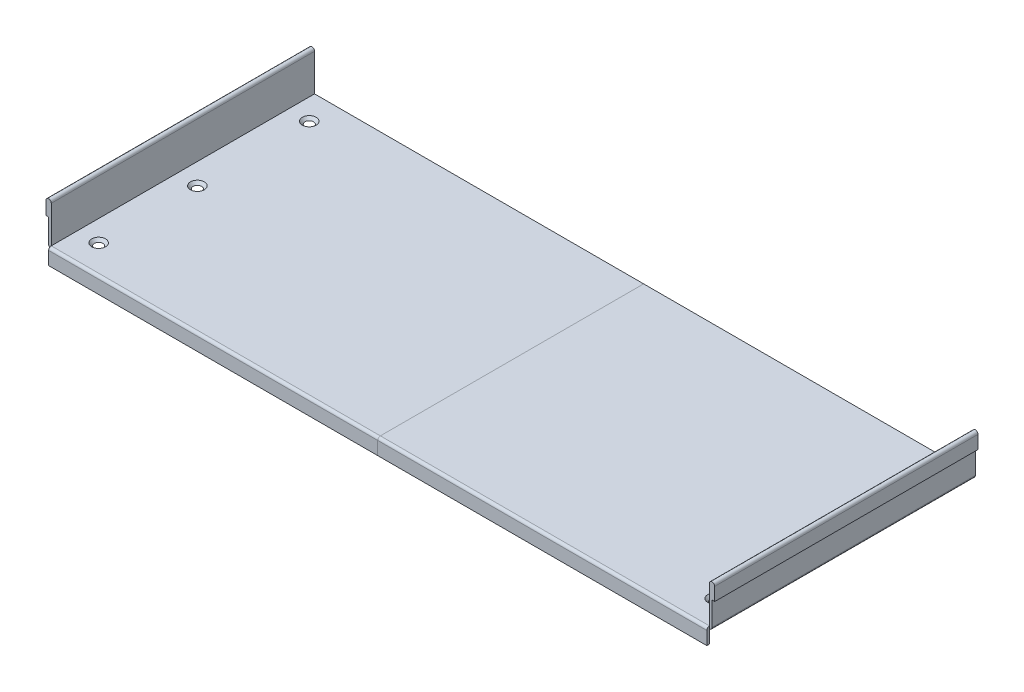
SolidWorks part; units mm, degrees
ref_plane "前基準面" through (0, 0, 0) normal (0, 0, 1) x (1, 0, 0)
ref_plane "上基準面" through (0, 0, 0) normal (0, 1, 0) x (1, 0, 0)
ref_plane "右基準面" through (0, 0, 0) normal (1, 0, 0) x (0, 0, -1)
ref_plane "平面1"
sketch "草圖1" plane through (0, 0, 0) normal (0, 0, 1) x (1, 0, 0)
  line L0 (0, 0) -> (0, -2)
  line L1 (0, -2) -> (250, -2)
  line L2 (252, 0) -> (252, 18)
  line L3 (252, 18) -> (254, 18)
  line L4 (254, 18) -> (254, 28)
  line L5 (250, 28) -> (250, 0)
  line L6 (250, 0) -> (0, 0)
  arc A0 (250, -2) -> (252, 0) centre (250, 0) ccw
  arc A1 (254, 28) -> (252, 30) centre (252, 28) ccw
  arc A2 (252, 30) -> (250, 28) centre (252, 28) ccw
extrude "擠出1" add sketch "草圖1" against normal blind 200
sketch "草圖2" plane through (0, 0, 0) normal (-1, 0, 0) x (0, 0, 1)
  line L0 (-200, -2) -> (-200, 28)
  line L1 (-204, 28) -> (-204, 18)
  line L2 (-204, 18) -> (-202, 18)
  line L3 (-202, 18) -> (-202, 0)
  arc A0 (-200, 28) -> (-202, 30) centre (-202, 28) ccw
  arc A1 (-202, 30) -> (-204, 28) centre (-202, 28) ccw
  arc A2 (-202, 0) -> (-200, -2) centre (-200, 0) ccw
extrude "擠出2" add sketch "草圖2" against normal up to surface rebuild error yes up to face at (250, 14, -100)
sketch "草圖3" plane through (0, 0, 0) normal (-1, 0, 0) x (0, 0, 1)
  line L0 (0, 0) -> (0, -12)
  line L1 (0, -12) -> (2, -12)
  line L2 (2, -12) -> (2, -2)
  arc A0 (2, -2) -> (0, 0) centre (0, -2) ccw
extrude "擠出3" add sketch "草圖3" against normal up to surface (250 mm away) up to face at (250, 14, -100)
ref_plane "平面2" through (234, 0, -200) normal (-1, 0, 0) x (0, 0, 1)
sketch "草圖4" plane through (234, 0, -200) normal (-1, 0, 0) x (0, 0, 1)
  line L0 (180, 0) -> (180, -2)
  line L1 (180, -2) -> (176.75, -2)
  line L2 (176.75, -2) -> (174.75, 0)
  line L3 (174.75, 0) -> (180, 0)
  line L4 (180, 0) -> (180, -2) construction
  line L5 (0, 0) -> (200, 0) construction
  line L6 (0, 28) -> (0, 0) construction
  dimension "D1" = 90
  dimension "D2" = 5.25
  dimension "D3" = 3.25
revolve "迴轉1" cut sketch "草圖4" angle 360 about L4
ref_plane "平面3" through (234, 0, -200) normal (-1, 0, 0) x (0, 0, 1)
sketch "草圖5" plane through (234, 0, -200) normal (-1, 0, 0) x (0, 0, 1)
  line L0 (20, 0) -> (20, -2)
  line L1 (20, -2) -> (16.75, -2)
  line L2 (16.75, -2) -> (14.75, 0)
  line L3 (14.75, 0) -> (20, 0)
  line L4 (20, 0) -> (20, -2) construction
  line L5 (0, 28) -> (0, 0) construction
  dimension "D1" = 20
  dimension "D2" = 183.25
  dimension "D3" = 185.25
revolve "迴轉2" cut sketch "草圖5" angle 360 about L4
ref_plane "平面4" through (234, 0, -200) normal (-1, 0, 0) x (0, 0, 1)
sketch "草圖6" plane through (234, 0, -200) normal (-1, 0, 0) x (0, 0, 1)
  line L0 (105, 0) -> (105, -2)
  line L1 (105, -2) -> (101.75, -2)
  line L2 (101.75, -2) -> (99.75, 0)
  line L3 (99.75, 0) -> (105, 0)
  line L4 (105, 0) -> (105, -2) construction
  line L5 (0, 0) -> (200, 0) construction
  line L6 (0, 28) -> (0, 0) construction
  dimension "D1" = 90
  dimension "D2" = 5.25
  dimension "D3" = 3.25
revolve "迴轉3" cut sketch "草圖6" angle 360 about L4
ref_plane "平面5" through (0, -1, -120) normal (-1, 0, 0) x (0, 1, 0)
mirror "鏡射1" about plane through (0, -1, -120) normal (-1, 0, 0) of bodies 105
